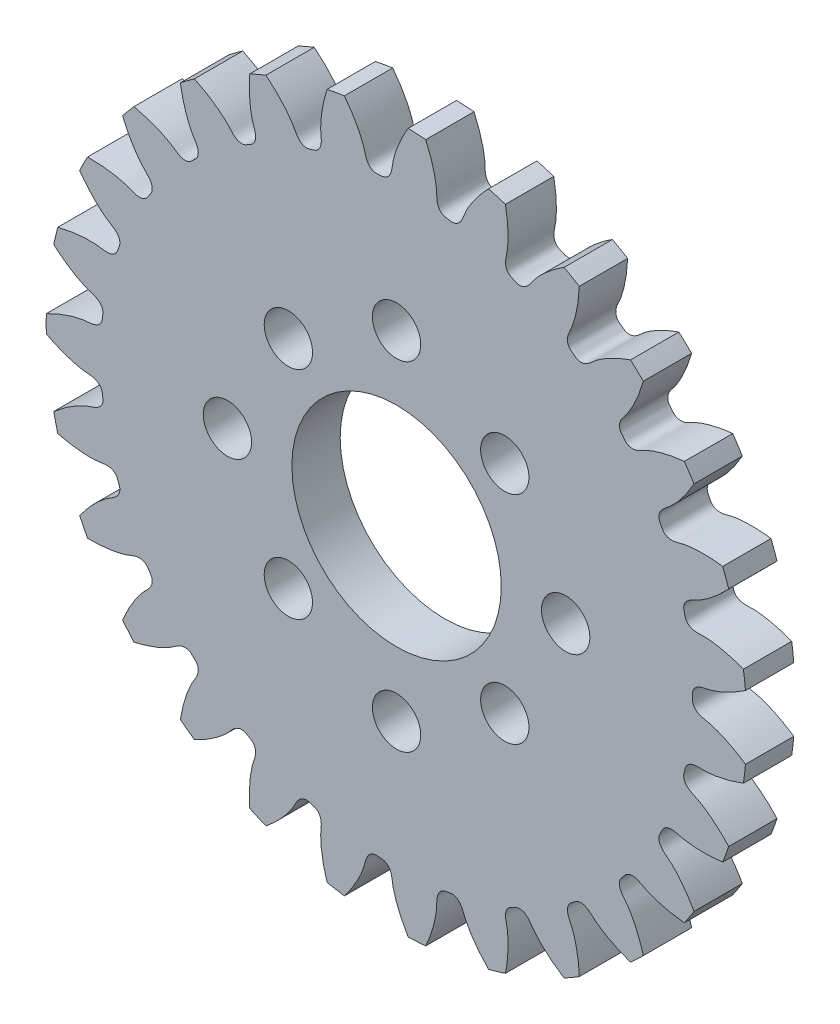
SolidWorks part; units mm, degrees
material "Thornel Mat VMA"
ref_plane "前视基准面" through (0, 0, 0) normal (0, 0, 1) x (1, 0, 0)
ref_plane "上视基准面" through (0, 0, 0) normal (0, 1, 0) x (1, 0, 0)
ref_plane "右视基准面" through (0, 0, 0) normal (1, 0, 0) x (0, 0, -1)
ref_axis "基准轴1" through (0, 0, 55) along (0, 0, -1)
sketch "旋转草图小直齿轮" plane through (0, 0, 0) normal (1, 0, 0) x (0, 0, -1)
  line L0 (0, 0) -> (-1.5, 0) construction
  line L1 (-1.5, 0) -> (-1.5, 21.75)
  line L2 (-1.5, 21.75) -> (1.5, 21.75)
  line L3 (1.5, 21.75) -> (1.5, 0)
  line L4 (1.5, 0) -> (-1.5, 0)
  line L5 (-55, 0) -> (55, 0) construction
  point P11 (0, 0)
  dimension "D1" = 21.75
  dimension "D2" = 3
revolve "小直齿轮" add sketch "旋转草图小直齿轮" angle 360 about L0
sketch "齿草图小直齿轮" plane through (0, 0, 0) normal (0, 0, 1) x (1, 0, 0)
  arc A0 (21.7303, 2.0309) -> (21.7303, -2.0309) centre (0, 0) cw
  spline S0 degree 3 poles (21.7303, -2.0309) (21.5019, -1.873) (21.1977, -1.6795) (20.815, -1.4669) (20.6085, -1.3597) (20.4126, -1.2648) (20.2278, -1.1817) (20.0547, -1.1095) (19.8935, -1.0476) (19.7449, -0.9952) (19.6091, -0.9516) (19.4866, -0.916) (19.3777, -0.8877) (19.2246, -0.8518) (19.0916, -0.8327) (18.9795, -0.8039) (18.9385, -0.7922) (18.8984, -0.7794) (18.8591, -0.7654) (18.8205, -0.7502) (18.7825, -0.7335) (18.7451, -0.7153) (18.708, -0.6952) (18.6713, -0.673) (18.6349, -0.6482) (18.5988, -0.6204) (18.563, -0.589) (18.5278, -0.5534) (18.4937, -0.5129) (18.4613, -0.4667) (18.4317, -0.4144) (18.4066, -0.3558) (18.3874, -0.2914) (18.3767, -0.2266) (18.3722, -0.129) (18.377, 0) (18.3722, 0.129) (18.3767, 0.2266) (18.3874, 0.2914) (18.4066, 0.3558) (18.4317, 0.4144) (18.4613, 0.4667) (18.4937, 0.5129) (18.5278, 0.5534) (18.563, 0.589) (18.5988, 0.6204) (18.6349, 0.6482) (18.6713, 0.673) (18.708, 0.6952) (18.7451, 0.7153) (18.7825, 0.7335) (18.8205, 0.7502) (18.8591, 0.7654) (18.8984, 0.7794) (18.9385, 0.7922) (18.9795, 0.8039) (19.0916, 0.8327) (19.2246, 0.8518) (19.3777, 0.8877) (19.4866, 0.916) (19.6091, 0.9516) (19.7449, 0.9952) (19.8935, 1.0476) (20.0547, 1.1095) (20.2278, 1.1817) (20.4126, 1.2648) (20.6085, 1.3597) (20.815, 1.4669) (21.1977, 1.6795) (21.5019, 1.873) (21.7303, 2.0309) knots 0 0 0 0 0.100325 0.130154 0.158175 0.184387 0.208793 0.23139 0.252179 0.271161 0.288335 0.303701 0.31726 0.32901 0.3605 0.365705 0.370832 0.375896 0.380912 0.385901 0.390886 0.395893 0.400954 0.406107 0.411393 0.416862 0.422569 0.428574 0.434936 0.441709 0.44893 0.456607 0.464704 0.473133 0.480264 0.5 0.519736 0.526867 0.535296 0.543393 0.55107 0.558291 0.565064 0.571426 0.577431 0.583138 0.588607 0.593893 0.599046 0.604107 0.609114 0.614099 0.619088 0.624104 0.629168 0.634295 0.6395 0.67099 0.68274 0.696299 0.711665 0.728839 0.747821 0.76861 0.791207 0.815613 0.841825 0.869846 0.899675 1 1 1 1
extrude "齿拉伸切除小直齿轮" cut sketch "齿草图小直齿轮" against normal blind 9.525 and the other way blind 9.525
pattern_circular "齿形小直齿轮" count 27 over 360 about axis through (0, 0, 55) along (0, 0, -1) of "齿拉伸切除小直齿轮"
sketch "孔旋转草图" plane through (0, 0, 0) normal (1, 0, 0) x (0, 0, -1)
  line L0 (0, 0) -> (1, 0) construction
  line L1 (-9.525, 0) -> (9.525, 0)
  line L2 (9.525, 0) -> (9.525, 6.5)
  line L3 (9.525, 6.5) -> (-9.525, 6.5)
  line L4 (-9.525, 6.5) -> (-9.525, 0)
  line L5 (0, 0) -> (-11.039, 0) construction
  dimension "D1" = 13
revolve "孔旋转切除" cut sketch "孔旋转草图" angle 360 about L0
sketch "辅助草图小直齿轮" plane through (0, 0, 0) normal (0, 0, 1) x (1, 0, 0)
  circle A0 centre (0, 0) radius 20.25 construction
  circle A1 centre (0, 0) radius 19.0288 construction
  circle A2 centre (0, 0) radius 19.1684 construction
  circle A3 centre (0, 0) radius 21.75 construction
  circle A4 centre (0, 0) radius 18.375 construction
  dimension "PitchDiameter" = 40.5
  dimension "BaseDiameter" = 38.0576
  dimension "FormDiameter" = 38.3368
  dimension "MajorDiameter" = 43.5
  dimension "MinorDiameter" = 36.75
sketch "草图1" plane through (0, 0, -1.5) normal (0, 0, -1) x (-1, 0, 0)
  circle A0 centre (0, 0) radius 10.5 construction
  circle A1 centre (10.5, 0) radius 1.5
  circle A2 centre (-10.5, 0) radius 1.5
  circle A3 centre (0, 10.5) radius 1.5
  circle A4 centre (0, -10.5) radius 1.5
  circle A17 centre (0, 0) radius 9.5 construction
  circle A18 centre (-6.7175, -6.7175) radius 1.5
  circle A19 centre (-6.7175, 6.7175) radius 1.5
  circle A20 centre (6.7175, 6.7175) radius 1.5
  circle A21 centre (6.7175, -6.7175) radius 1.5
  point P23 (0, 0)
  dimension "D1" = 21
  dimension "D2" = 3
  dimension "D3" = 19
  dimension "D4" = 4
  dimension "D5" = 3
extrude "切除-拉伸1" cut sketch "草图1" against normal up to next
